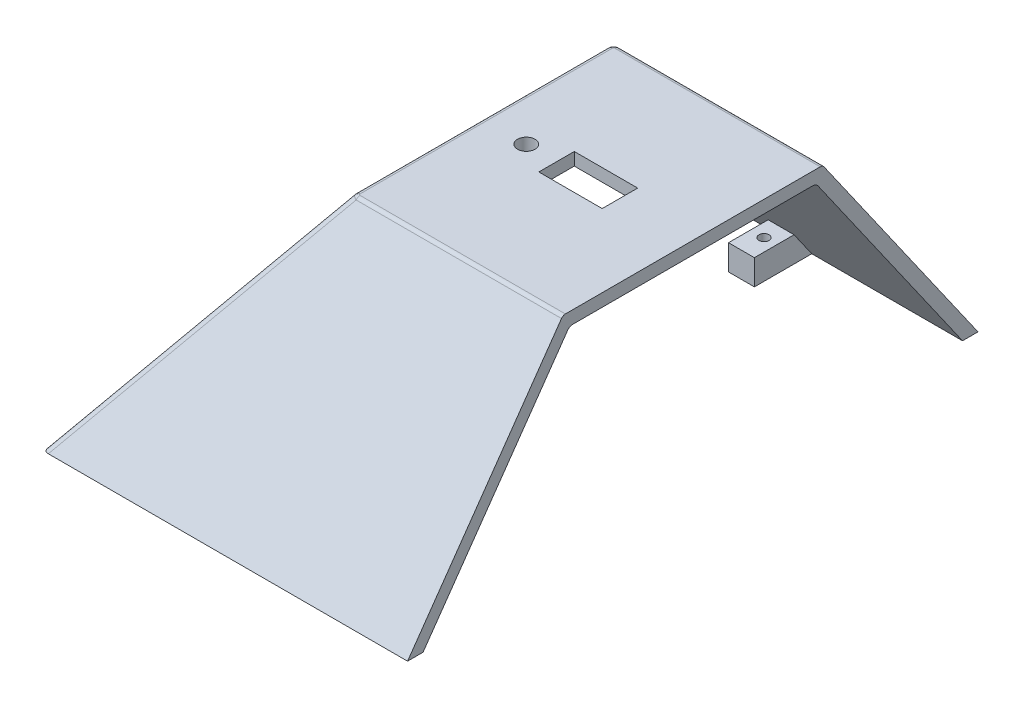
SolidWorks part; units mm, degrees
ref_plane "Alzado" through (0, 0, 0) normal (0, 0, 1) x (1, 0, 0)
ref_plane "Planta" through (0, 0, 0) normal (0, 1, 0) x (1, 0, 0)
ref_plane "Vista lateral" through (0, 0, 0) normal (1, 0, 0) x (0, 0, -1)
sketch "Croquis1" plane through (0, 0, 0) normal (0, 1, 0) x (1, 0, 0)
  line L1 (90, -90) -> (-90, -90)
  line L2 (90, -90) -> (90, 90)
  line L3 (90, 90) -> (-90, 90)
  line L4 (-90, -90) -> (-90, 90)
  line L5 (90, -90) -> (-90, 90) construction
  line L6 (90, 90) -> (-90, -90) construction
  point P0 (0, 0)
  dimension "D1" = 180
  dimension "D2" = 180
extrude "Saliente-Extruir1" add sketch "Croquis1" along normal blind 70
sketch "Croquis3" plane through (-90, 0, 0) normal (-1, 0, 0) x (0, 0, 1)
  line L0 (-90, 0) -> (-90, 70)
  line L1 (-90, 70) -> (-40.9855, 70)
  line L2 (-90, 70) -> (90, 70) construction
  line L3 (-40.9855, 70) -> (-90, 0)
  line L4 (90, 0) -> (90, 70)
  line L5 (90, 70) -> (40.9855, 70)
  line L6 (40.9855, 70) -> (90, 0)
  dimension "D1" = 35
  dimension "D2" = 35
extrude "Cortar-Extruir2" cut sketch "Croquis3" against normal up to next
sketch "Croquis2" plane through (0, 0, 90) normal (0, 0, 1) x (1, 0, 0)
  line L0 (90, 0) -> (90, 80)
  line L1 (90, 80) -> (33.9834, 80)
  line L2 (-90, 80) -> (90, 80) construction
  line L3 (33.9834, 80) -> (90, 0)
  line L4 (-90, 80) -> (-33.9834, 80)
  line L5 (-33.9834, 80) -> (-90, 0)
  line L6 (-90, 0) -> (-90, 80)
  dimension "D1" = 35
  dimension "D2" = 35
extrude "Cortar-Extruir1" cut sketch "Croquis2" against normal up to next
shell "Vaciado1" thickness 4 removed face at (0, 0, 0)
sketch "Croquis4" plane through (60.3909, 42.2862, 0) normal (0.8192, 0.5736, 0) x (0, 0, -1)
  line L0 (-90, -51.6219) -> (-40.9855, 33.8323)
  line L1 (-40.9855, 33.8323) -> (40.9855, 33.8323)
  line L2 (40.9855, 33.8323) -> (90, -51.6219)
  line L3 (90, -51.6219) -> (-90, -51.6219)
extrude "Cortar-Extruir3" cut sketch "Croquis4" against normal up to next
sketch "Croquis7" plane through (0, 0, 0) normal (0, 0, 1) x (1, 0, 0)
  line L0 (90, 0) -> (25, 0)
  line L1 (-90, 0) -> (90, 0) construction
  line L2 (25, 0) -> (25, 70)
  line L3 (40.9855, 70) -> (-40.9855, 70) construction
  line L4 (25, 70) -> (40.9855, 70)
  line L5 (40.9855, 70) -> (90, 0)
  dimension "D1" = 65
extrude "Cortar-Extruir5" cut sketch "Croquis7" against normal up to next and the other way up to next
ref_plane "Plano1" through (0, 0, 67) normal (0, 0, 1) x (1, 0, 0)
sketch "Croquis9" plane through (0, 0, 67) normal (0, 0, 1) x (1, 0, 0)
  line L0 (-85.1169, 0) -> (25, 0) construction
  line L1 (-22.5618, 0) -> (-30.7314, 0)
  line L2 (-22.5618, 0) -> (-22.5618, 8)
  line L3 (-22.5618, 8) -> (-30.7314, 8)
  line L4 (-30.7314, 0) -> (-30.7314, 8)
  line L5 (-22.5618, 0) -> (-30.7314, 8) construction
  line L6 (-22.5618, 8) -> (-30.7314, 0) construction
  line L7 (-26.6466, 4) -> (-26.6466, -38.2733) construction
  point P4 (-26.6466, 4)
  dimension "D1" = 8
extrude "Saliente-Extruir2" add sketch "Croquis9" along normal up to next
sketch "Croquis11" plane through (0, 0, 0) normal (0, -1, 0) x (1, 0, 0)
  circle A0 centre (-26.5104, 74) radius 1.585
extrude "Cortar-Extruir7" cut sketch "Croquis11" against normal up to next
mirror "Simetría1" about plane through (0, 0, 0) normal (0, 0, 1) of "Cortar-Extruir7", "Saliente-Extruir2"
sketch "Croquis12" plane through (0, 70, 0) normal (0, 1, 0) x (1, 0, 0)
  line L0 (25, 40.9855) -> (-40.9855, 40.9855) construction
  line L1 (-17.9905, 5.6005) -> (2.0095, 5.6005)
  line L2 (-17.9905, 5.6005) -> (-17.9905, -5.5995)
  line L3 (-17.9905, -5.5995) -> (2.0095, -5.5995)
  line L4 (2.0095, 5.6005) -> (2.0095, -5.5995)
  line L5 (-17.9905, 5.6005) -> (2.0095, -5.5995) construction
  line L6 (-17.9905, -5.5995) -> (2.0095, 5.6005) construction
  line L8 (-40.9855, 40.9855) -> (-40.9855, -40.9855) construction
  point P4 (-7.9905, 0.0005)
  dimension "D1" = 11.2
  dimension "D2" = 20
  dimension "D3" = 40.985
  dimension "D4" = 32.995
extrude "Cortar-Extruir8" cut sketch "Croquis12" against normal up to next
fillet "Redondeo1" radius 2 7 edges at (-6.9516, 66, -38.9032) (-6.9516, 66, 38.9032) (-65.4927, 35, 65.4927) (-38.9032, 66, 0) (-62.0101, 33, -62.0101) (-65.4927, 35, -65.4927) (-62.0101, 33, 62.0101)
sketch "Croquis13" plane through (0, 70, 0) normal (0, 1, 0) x (1, 0, 0)
  circle A0 centre (-27.5466, 0) radius 2.75
  dimension "D1" = 5.5
extrude "Cortar-Extruir9" cut sketch "Croquis13" against normal up to next
fillet "Redondeo2" radius 1.5 5 edges at (-7.1736, 70, -40.9855) (-40.5342, 70, -40.5342) (-7.1736, 70, 40.9855) (-40.5342, 70, 40.5342) (-40.9855, 70, 0)
